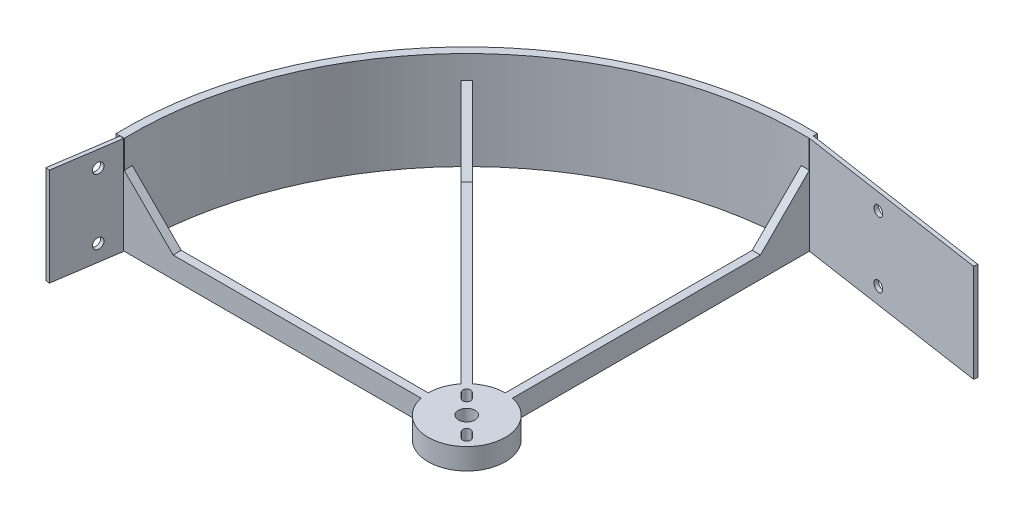
SolidWorks part; units mm, degrees
material "ABS"
ref_plane "Front Plane" through (0, 0, 0) normal (0, 0, 1) x (1, 0, 0)
ref_plane "Top Plane" through (0, 0, 0) normal (0, 1, 0) x (1, 0, 0)
ref_plane "Right Plane" through (0, 0, 0) normal (1, 0, 0) x (0, 0, -1)
sketch "Sketch1" plane through (0, 0, 0) normal (0, 1, 0) x (1, 0, 0)
  line L0 (0, 130.175) -> (0, 9.3426)
  line L1 (3.175, 9.3426) -> (3.175, 130.1363)
  line L2 (-92.0476, 92.0476) -> (0, 0) construction
  line L3 (-90.9182, 93.1633) -> (-5.7657, 8.0107)
  line L4 (-9.7388, -3.175) -> (-130.1363, -3.175)
  line L5 (-130.175, 0) -> (-9.3426, 0)
  line L6 (3.175, 9.3426) -> (3.175, 130.1363)
  line L7 (3.175, 130.1363) -> (3.175, 133.3122)
  line L8 (-130.1363, -3.175) -> (-133.3122, -3.175)
  line L9 (0, 0) -> (-130.175, 0) construction
  line L10 (-8.0089, 5.7638) -> (-93.1633, 90.9182)
  line L11 (0, 0) -> (0, 146.05) construction
  circle A0 centre (0, 0) radius 15
  arc A1 (3.175, 130.1363) -> (-130.1363, -3.175) centre (0, 0) ccw
  arc A2 (3.175, 133.3122) -> (-133.3122, -3.175) centre (0, 0) ccw
  point P21 (0, 0)
  dimension "D1" = 30
  dimension "D2" = 133.35
  dimension "D4" = 3.175
  dimension "D6" = 1.5875
  dimension "D3" = 3.175
  dimension "D7" = 1.5875
  dimension "D5" = 3.175
extrude "Boss-Extrude2" add sketch "Sketch1" along normal blind 8.255 contours A0
extrude "Boss-Extrude3" add sketch "Sketch1<6>" along normal blind 8.255 contours L5 A1 L4 A0 | L6 A1 L0 A0 | A1 L10 A0 region at (1.5882, 0, -72.5246) region at (-51.3161, 0, -51.3161) region at (-72.5246, 0, 1.5882)
sketch "Sketch1<6>" plane through (0, 0, 0) normal (0, 1, 0) x (1, 0, 0) same geometry as "Sketch1"
extrude "Boss-Extrude4" add sketch "Sketch1<7>" along normal blind 38.1 contours L7 A2 L8 A1 region at (-49.8095, 0, -122.3558)
sketch "Sketch1<7>" plane through (0, 0, 0) normal (0, 1, 0) x (1, 0, 0) same geometry as "Sketch1"
ref_plane "Plane1" through (-63.4806, 0, -63.4806) normal (0.7071, 0, 0.7071) x (0.7071, 0, -0.7071)
sketch "Sketch5" plane through (0, 8.255, 0) normal (0, 1, 0) x (1, 0, 0)
  line L0 (0, 0) -> (-92.0476, 92.0476) construction
  line L1 (0, 0) -> (15.8128, 15.8128) construction
  line L3 (-5.5678, 5.5678) -> (-7.723, 7.723) construction
  line L4 (-6.6454, 4.4901) -> (-8.8007, 6.6454)
  line L5 (-4.4901, 6.6454) -> (-6.6454, 8.8007)
  line L6 (5.5678, -5.5678) -> (7.723, -7.723) construction
  line L7 (4.4901, -6.6454) -> (6.6454, -8.8007)
  line L8 (6.6454, -4.4901) -> (8.8007, -6.6454)
  arc A1 (-6.6454, 4.4901) -> (-4.4901, 6.6454) centre (-5.5678, 5.5678) ccw
  arc A2 (-6.6454, 8.8007) -> (-8.8007, 6.6454) centre (-7.723, 7.723) ccw
  arc A3 (4.4901, -6.6454) -> (6.6454, -4.4901) centre (5.5678, -5.5678) cw
  arc A4 (8.8007, -6.6454) -> (6.6454, -8.8007) centre (7.723, -7.723) cw
  circle A6 centre (0, 0) radius 3.25
  point P8 (-6.6454, 6.6454)
  point P15 (6.6454, -6.6454)
  point P18 (0, 0)
  dimension "D3" = 3.048
  dimension "D1" = 7.874
  dimension "D2" = 3.048
extrude "Cut-Extrude3" cut sketch "Sketch5" against normal blind 63.5
sketch "Sketch6" plane through (0, 0, 3.175) normal (0, 0, 1) x (1, 0, 0)
  line L0 (-14.6601, 0) -> (-133.3122, 0) construction
  line L1 (-130.1363, 38.1) -> (-131.7242, 38.1)
  line L2 (-130.1363, 38.1) -> (-130.1363, 0)
  line L3 (-130.1363, 0) -> (-131.7242, 0)
  line L4 (-131.7242, 38.1) -> (-131.7242, 0)
  line L5 (-130.1363, 38.1) -> (-133.3122, 38.1) construction
  point P7 (-131.7242, 38.1)
sketch "Sketch7" plane through (3.175, 0, 0) normal (1, 0, 0) x (0, 0, -1)
  line L0 (14.6601, 0) -> (133.3122, 0) construction
  line L1 (130.1363, 38.1) -> (131.7242, 38.1)
  line L2 (130.1363, 38.1) -> (130.1363, 0)
  line L3 (130.1363, 0) -> (131.7242, 0)
  line L4 (131.7242, 38.1) -> (131.7242, 0)
  line L5 (130.1363, 38.1) -> (133.3122, 38.1) construction
  line L6 (130.1363, 38.1) -> (130.1363, 8.255) construction
  point P7 (131.7242, 38.1)
ref_plane "Plane2" through (0, 0, 0) normal (0, 0, -1) x (-1, 0, 0)
sketch "Sketch10" plane through (0, 0, 0) normal (0, 0, -1) x (-1, 0, 0)
  line L0 (130.175, 27.305) -> (130.175, 8.255)
  line L4 (130.175, 8.255) -> (130.175, 38.1) construction
  line L5 (130.175, 8.255) -> (111.125, 8.255)
  line L6 (130.175, 8.255) -> (15, 8.255) construction
  line L7 (111.125, 8.255) -> (130.175, 27.305)
  dimension "D1" = 19.05
  dimension "D2" = 45
extrude "Boss-Extrude9" add sketch "Sketch10" against normal blind 3.175
ref_plane "Plane3" through (1.1225, 0, -1.1225) normal (0.7071, 0, -0.7071) x (-0.7071, 0, -0.7071)
ref_plane "Plane4" through (0, 0, 0) normal (-1, 0, 0) x (0, 0, 1)
sketch "Sketch13" plane through (0, 0, 0) normal (-1, 0, 0) x (0, 0, 1)
  line L0 (-130.175, 27.305) -> (-111.125, 8.255)
  line L1 (-130.175, 27.305) -> (-130.175, 8.255)
  line L2 (-130.175, 8.255) -> (-15, 8.255) construction
  line L3 (-130.175, 8.255) -> (-111.125, 8.255)
  line L4 (-130.175, 38.1) -> (-130.175, 8.255) construction
  dimension "D1" = 45
  dimension "D2" = 19.05
extrude "Boss-Extrude11" add sketch "Sketch13" against normal blind 3.175
sketch "Sketch14" plane through (1.1225, 0, -1.1225) normal (0.7071, 0, -0.7071) x (-0.7071, 0, -0.7071)
  line L0 (133.3403, 8.255) -> (111.1153, 8.255)
  line L1 (130.1653, 8.255) -> (14.9158, 8.255) construction
  line L2 (133.3403, 8.255) -> (133.3403, 32.3947)
  line L3 (133.3403, 32.3947) -> (111.1153, 8.255)
  dimension "D1" = 22.225
extrude "Boss-Extrude14" add sketch "Sketch14" against normal blind 3.175
ref_plane "Plane5" through (-128.3822, 0, -19.1869) normal (-0.989, 0, -0.1478) x (0, -1, 0)
sketch "Sketch15" plane through (-128.3822, 0, -19.1869) normal (-0.989, 0, -0.1478) x (0, -1, 0)
  line L1 (-38.1, 48.0102) -> (0, 48.0102)
  line L2 (-38.1, 48.0102) -> (-38.1, 22.6102)
  line L3 (-38.1, 22.6102) -> (0, 22.6102)
  line L4 (0, 48.0102) -> (0, 22.6102)
  dimension "D1" = 25.4
extrude "Boss-Extrude15" add sketch "Sketch15" against normal blind 1.524
ref_plane "Plane6" through (19.3256, 0, -129.3105) normal (0.1478, 0, -0.989) x (0, -1, 0)
sketch "Sketch16" plane through (19.3256, 0, -129.3105) normal (0.1478, 0, -0.989) x (0, -1, 0)
  line L1 (-38.1, 16.33) -> (0, 16.33)
  line L2 (-38.1, 16.33) -> (-38.1, -59.87)
  line L3 (-38.1, -59.87) -> (0, -59.87)
  line L4 (0, 16.33) -> (0, -59.87)
  dimension "D1" = 76.2
extrude "Boss-Extrude16" add sketch "Sketch16" against normal blind 1.524
sketch "Sketch17" plane through (19.3256, 0, -129.3105) normal (0.1478, 0, -0.989) x (-0.989, 0, -0.1478)
  line L0 (16.5647, 38.1) -> (16.5647, 0) construction
  line L1 (16.33, 38.1) -> (-59.87, 38.1) construction
  line L2 (19.05, 19.05) -> (-59.87, 19.05) construction
  line L3 (-59.87, 38.1) -> (-59.87, 0) construction
  circle A0 centre (-15.8102, 31.75) radius 1.985
  circle A1 centre (-15.8102, 6.35) radius 1.985
  dimension "D1" = 32.3748
  dimension "D3" = 3.97
  dimension "D2" = 6.35
extrude "Cut-Extrude4" cut sketch "Sketch17" against normal blind 2.54
sketch "Sketch18" plane through (-128.3822, 0, -19.1869) normal (-0.989, 0, -0.1478) x (-0.1478, 0, 0.989)
  line L0 (22.3755, 38.1) -> (22.3755, 0) construction
  line L1 (25.4, 19.05) -> (48.0102, 19.05) construction
  line L2 (48.0102, 0) -> (48.0102, 38.1) construction
  circle A0 centre (31.2655, 31.75) radius 1.985
  circle A1 centre (31.2655, 6.35) radius 1.985
  dimension "D1" = 3.97
  dimension "D2" = 8.89
extrude "Cut-Extrude5" cut sketch "Sketch18" against normal blind 2.54
